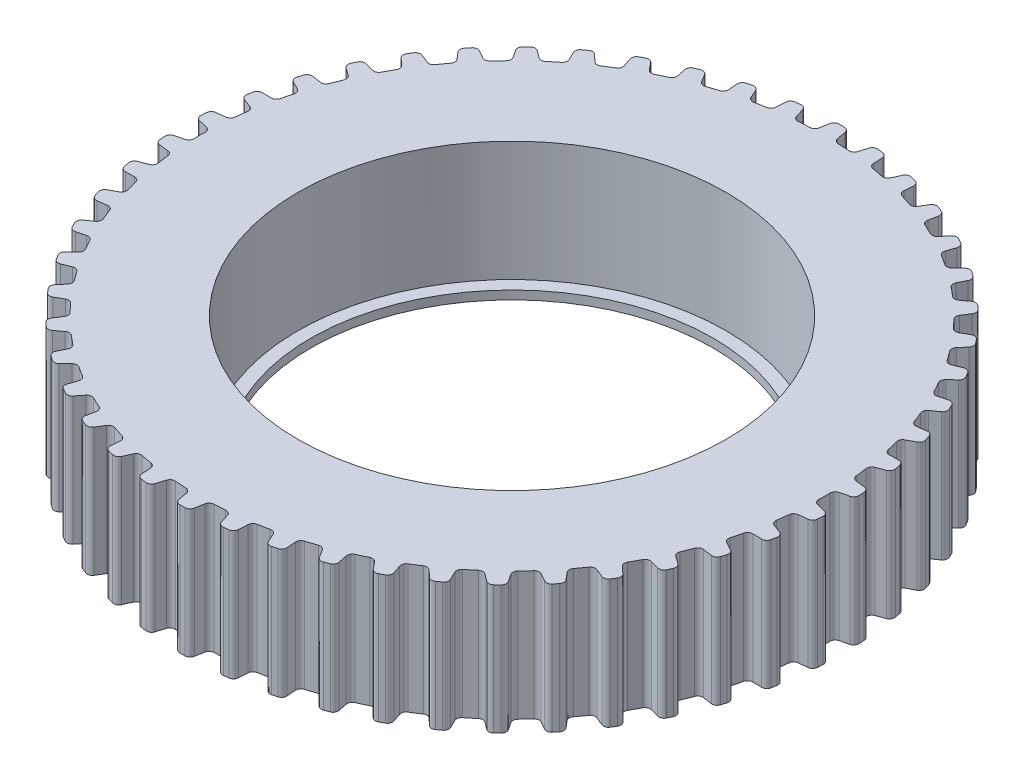
SolidWorks part; units mm, degrees
ref_plane "Front Plane" through (0, 0, 0) normal (0, 0, 1) x (1, 0, 0)
ref_plane "Top Plane" through (0, 0, 0) normal (0, 1, 0) x (1, 0, 0)
ref_plane "Right Plane" through (0, 0, 0) normal (1, 0, 0) x (0, 0, -1)
sketch "Sketch2" plane through (0, 0, 0) normal (0, 1, 0) x (1, 0, 0)
  circle A0 centre (0, 0) radius 25
  circle A1 centre (0, 0) radius 36.5
  dimension "D1" = 50
  dimension "D2" = 73
extrude "Boss-Extrude1" add sketch "Sketch2" along normal blind 15
sketch "Sketch3" plane through (0, 15, 0) normal (0, 1, 0) x (1, 0, 0)
  line L0 (0, 0) -> (0, 38.5) construction
  line L1 (-0.8044, 38.4916) -> (-1.1588, 36.4816)
  line L2 (0.8044, 38.4916) -> (1.1588, 36.4816)
  line L3 (-0.9816, 37.4866) -> (0, 0) construction
  line L4 (0.9816, 37.4866) -> (0, 0) construction
  circle A0 centre (0, 0) radius 37.5 construction
  arc A1 (0.8044, 38.4916) -> (-0.8044, 38.4916) centre (0, 0) ccw
  circle A2 centre (0, 0) radius 36.5 construction
  circle A3 centre (0, 0) radius 38.5 construction
  circle A4 centre (0, 0) radius 36.5 construction
  arc A5 (-1.1588, 36.4816) -> (1.1588, 36.4816) centre (0, 0) cw
  point P14 (0, 40.5)
  dimension "D2" = 1
  dimension "D3" = 1
  dimension "D4" = 10
  dimension "D5" = 3
extrude "Boss-Extrude2" add sketch "Sketch3" against normal up to surface (15 mm away) up to face at (0, 0, 36.5)
fillet "Fillet1" radius 0.6 4 edges at (1.1588, 7.5, -36.4816) (-1.1588, 7.5, -36.4816) (0.8044, 7.5, -38.4916) (-0.8044, 7.5, -38.4916)
pattern_circular "CirPattern4" count 50 over 360 about axis through (0, 15, 0) along (0, -1, 0) of "Boss-Extrude2", "Fillet1" reverse direction yes
sketch "Sketch4" plane through (0, 0, 0) normal (0, -1, 0) x (1, 0, 0)
  circle A0 centre (0, 0) radius 25 construction
  circle A1 centre (0, 0) radius 25
  circle A2 centre (0, 0) radius 23.5
  dimension "D1" = 1.5
extrude "Boss-Extrude3" add sketch "Sketch4" against normal blind 1
